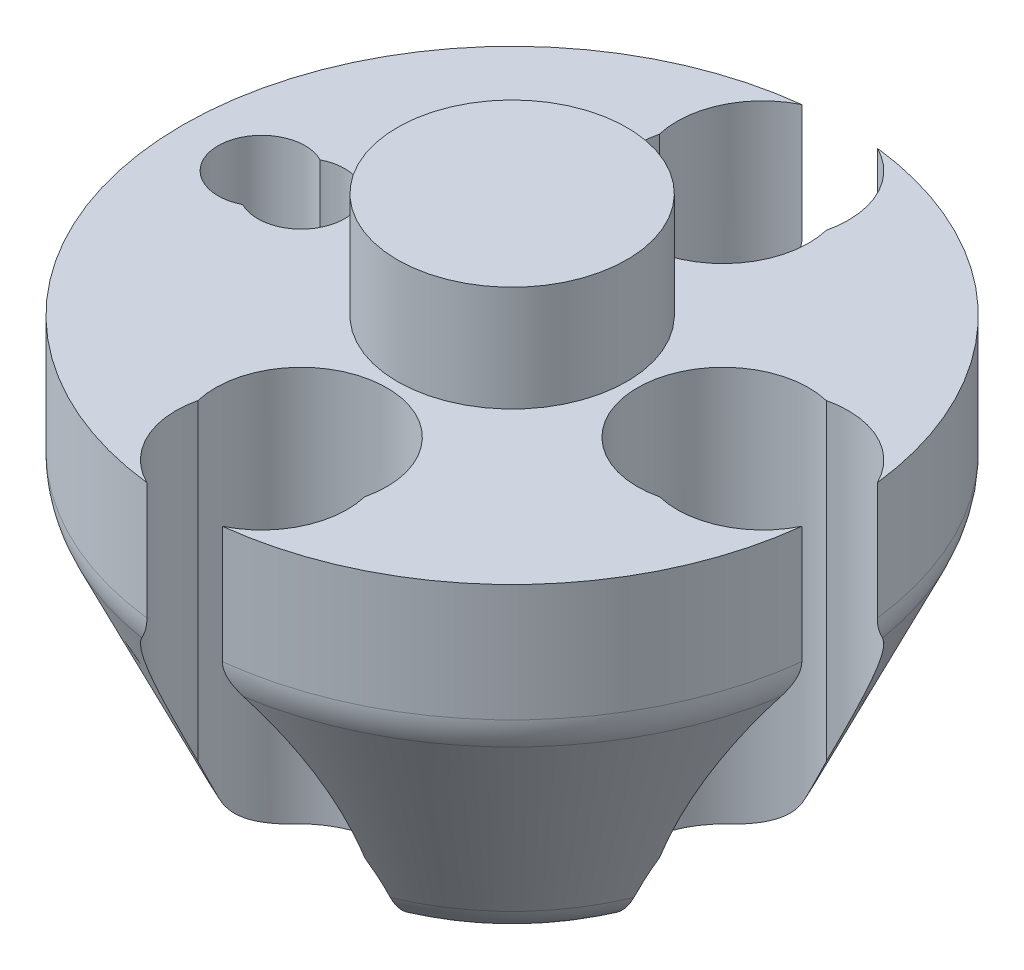
SolidWorks part; units mm, degrees
ref_plane "Спереди" through (0, 0, 0) normal (0, 0, 1) x (1, 0, 0)
ref_plane "Сверху" through (0, 0, 0) normal (0, 1, 0) x (1, 0, 0)
ref_plane "Справа" through (0, 0, 0) normal (1, 0, 0) x (0, 0, -1)
sketch "Эскиз1" plane through (0, 0, 0) normal (0, 1, 0) x (1, 0, 0)
  line L0 (-457.4451, 0) -> (22318.6456, 0) construction
  line L1 (0, -455.5218) -> (0, 22320.5689) construction
  line L2 (0, 0) -> (0, 8) construction
  line L3 (0, 0) -> (8, 0) construction
  circle A0 centre (0, 0) radius 12.5
  circle A1 centre (0, 9.5) radius 3.25
  circle A2 centre (0, 8) radius 3.25
  circle A4 centre (9.5, 0) radius 3.25
  circle A5 centre (8, 0) radius 3.25
  circle A6 centre (0, -9.5) radius 3.25
  circle A7 centre (0, -8) radius 3.25
  circle A10 centre (0, 0) radius 4.35
  circle A11 centre (-9.5, 0) radius 1.65
  circle A12 centre (-8, 0) radius 1.65
  point P27 (0, 0)
  dimension "D2" = 25
  dimension "D3" = 6.5
  dimension "D4" = 8.7
  dimension "D1" = 1.5
  dimension "D5" = 8
  dimension "D6" = 3
extrude "Бобышка-Вытянуть1" add sketch "Эскиз1" along normal blind 5 contours A0 A12 A7 A6 A5 A4 A2 A1 | A10 region at (11.0371, 0, -3.2573)
extrude "Бобышка-Вытянуть2" add sketch "Эскиз1<4>" along normal blind 4 from surface contours A10 region at (0, 0, 0) starting at face at (2.6418, 5, 0)
sketch "Эскиз1<4>" plane through (0, 0, 0) normal (0, 1, 0) x (1, 0, 0) same geometry as "Эскиз1"
sketch "Эскиз4" plane through (0, 0, 0) normal (0, -1, 0) x (1, 0, 0)
  circle A0 centre (0, 0) radius 3.1
  arc A2 (-1.4315, 12.4178) -> (-1.4315, -12.4178) centre (0, 0) ccw construction
  point P4 (0, 0)
  dimension "D1" = 6.2
extrude "Вырез-Вытянуть2" cut sketch "Эскиз4" against normal blind 7
sketch "Эскиз5" plane through (0, 0, 0) normal (0, -1, 0) x (1, 0, 0)
  circle A0 centre (0, 0) radius 12.5
extrude "Бобышка-Вытянуть3" add sketch "Эскиз5" along normal blind 10 draft 25
extrude "Вырез-Вытянуть3" cut sketch "Эскиз1<6>" against normal blind 10 contours A1 A2 | A1 A2 | A2 A1 A0 | A12 A11 | A12 A11 | A11 A12 | A4 A5 | A4 A5 | A5 A4 A0 | A6 A7 | A7 A6 A0 | A6 A7 region at (11.2593, 0, 0) region at (0, 0, -11.2593) region at (8.75, 0, 0) region at (6.1744, 0, 0) region at (0, 0, 11.2593) region at (0, 0, -8.75) region at (0, 0, -6.1744) region at (0, 0, 6.1744) region at (0, 0, 8.75) region at (-8.75, 0, 0) region at (-7.4063, 0, 0) region at (-10.0937, 0, 0)
sketch "Эскиз1<6>" plane through (0, 0, 0) normal (0, 1, 0) x (1, 0, 0) same geometry as "Эскиз1"
extrude "Вырез-Вытянуть4" cut sketch "Эскиз4<2>" along normal blind 10
sketch "Эскиз4<2>" plane through (0, 0, 0) normal (0, -1, 0) x (1, 0, 0) same geometry as "Эскиз4"
fillet "Скругление1" radius 2.5 5 edges at (8.8388, 0, 8.8388) (8.8388, 0, -8.8388) (-12.5, 0, 0) (5.5415, -10, -5.5415) (5.5415, -10, 5.5415)
fillet "Скругление2" radius 2.5 1 edges at (-6.0798, -10, -4.9451)
sketch "Эскиз6" plane through (0, 5, 0) normal (0, 1, 0) x (1, 0, 0)
  arc A0 (-8.75, -2.6977) -> (-8.75, 2.6977) centre (-8, 0) ccw
  arc A1 (-8.75, 2.6977) -> (-8.75, -2.6977) centre (-9.5, 0) ccw
  dimension "D1" = 5.6
extrude "Вырез-Вытянуть5" cut sketch "Эскиз6" against normal through all from offset 5 offset against normal yes
